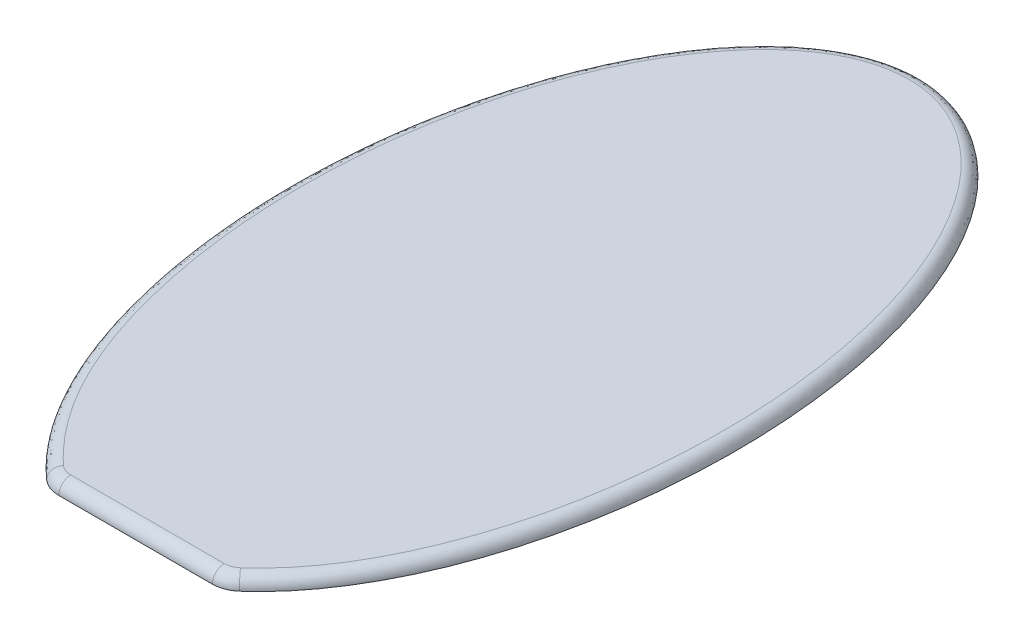
SolidWorks part; units mm, degrees
ref_plane "Front Plane" through (0, 0, 0) normal (0, 0, 1) x (1, 0, 0)
ref_plane "Top Plane" through (0, 0, 0) normal (0, 1, 0) x (1, 0, 0)
ref_plane "Right Plane" through (0, 0, 0) normal (1, 0, 0) x (0, 0, -1)
sketch "Sketch1" plane through (0, 0, 0) normal (0, 1, 0) x (1, 0, 0)
  ellipse E0 centre (0, 0) end of major axis (0, -34.925) minor radius 19.05
  dimension "D1" = 38.1
  dimension "D2" = 69.85
extrude "Boss-Extrude1" add sketch "Sketch1" along normal blind 1.016
sketch "Sketch2" plane through (0, 1.016, 0) normal (0, 1, 0) x (1, 0, 0)
  line L0 (-7.466, -32.131) -> (7.466, -32.131)
  ellipse E0 centre (0, 0) end of major axis (0, -34.925) minor radius 19.05 construction
  ellipse E1 centre (0, 0) end of major axis (0, -34.925) minor radius 19.05 (-7.466, -32.131) -> (7.466, -32.131) ccw
  dimension "D1" = 67.056
extrude "Cut-Extrude1" cut sketch "Sketch2" against normal through all
fillet "Fillet1" radius 2.54 2 edges at (-7.466, 0.508, 32.131) (7.466, 0.508, 32.131)
fillet "Fillet2" radius 1.016 4 edges at (7.4471, 1.016, 31.968) (-7.4471, 1.016, 31.968) (0, 1.016, 32.131) (0, 1.016, -34.925)
